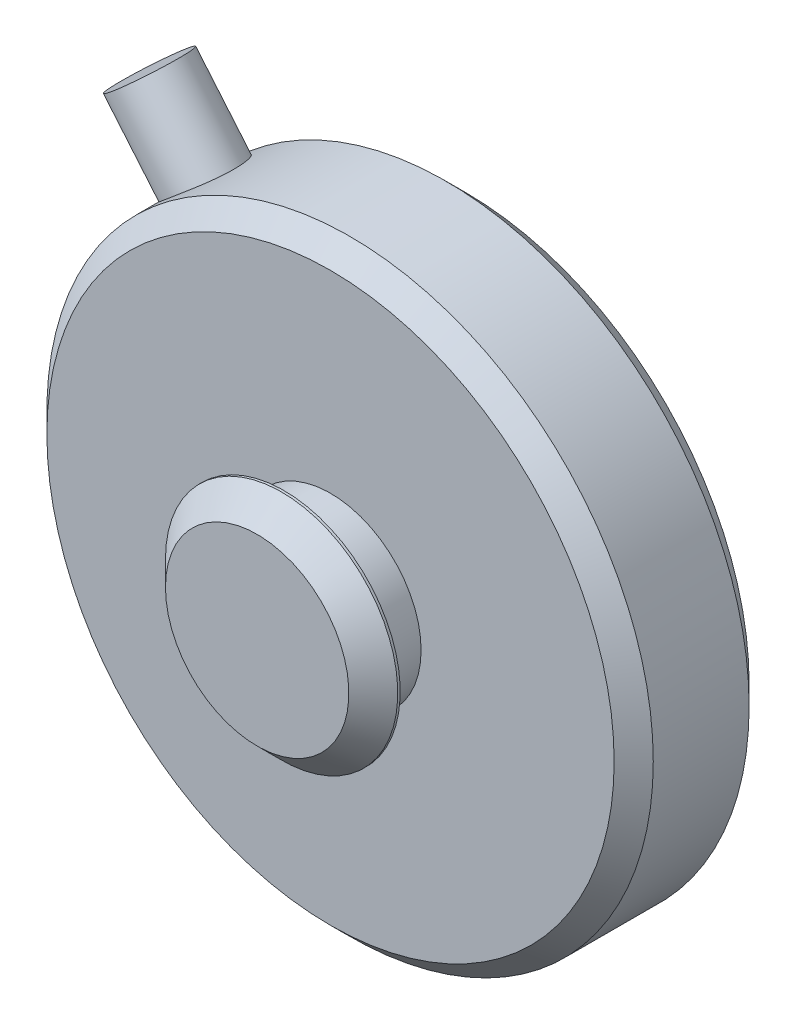
SolidWorks part; units mm, degrees
material "Plain Carbon Steel"
ref_plane "Front Plane" through (0, 0, 0) normal (0, 0, 1) x (1, 0, 0)
ref_plane "Top Plane" through (0, 0, 0) normal (0, 1, 0) x (1, 0, 0)
ref_plane "Right Plane" through (0, 0, 0) normal (1, 0, 0) x (0, 0, -1)
sketch "Sketch1" plane through (0, 0, 0) normal (0, 0, 1) x (1, 0, 0)
  circle A0 centre (0, 0) radius 157.48
  dimension "D1" = 314.96
extrude "Extrude1" add sketch "Sketch1" along normal blind 70.104
sketch "Sketch2" plane through (0, 0, 70.104) normal (0, 0, 1) x (1, 0, 0)
  circle A0 centre (0, 0) radius 47.0535
  dimension "D1" = 94.107
extrude "Extrude2" add sketch "Sketch2" along normal blind 24.13
sketch "Sketch3" plane through (0, 0, 0) normal (0, 0, -1) x (-1, 0, 0)
  circle A0 centre (0, 0) radius 15.0114
  dimension "D1" = 30.0228
extrude "Extrude3" add sketch "Sketch3" along normal blind 13.462
sketch "Sketch4" plane through (0, 0, -13.462) normal (0, 0, -1) x (-1, 0, 0)
  circle A0 centre (0, 0) radius 24.511
  dimension "D1" = 49.022
extrude "Extrude4" add sketch "Sketch4" along normal blind 6.35
sketch "Sketch5" plane through (0, 0, -19.812) normal (0, 0, -1) x (-1, 0, 0)
  circle A0 centre (0, 0) radius 15.875
  dimension "D1" = 31.75
extrude "Extrude5" add sketch "Sketch5" along normal blind 6.858
sketch "Sketch6" plane through (0, 0, 0) normal (0, 0, -1) x (-1, 0, 0)
  circle A0 centre (0, -38.1) radius 3.175
  dimension "D2" = 6.35
  dimension "D1" = 38.1
extrude "Cut-Extrude1" cut sketch "Sketch6" against normal blind 11.43
pattern_circular "CirPattern1" count 5 over 360 about axis through (0, 0, 70.104) along (0, 0, -1) of "Cut-Extrude1"
sketch "Sketch7" plane through (0, 0, 94.234) normal (0, 0, 1) x (1, 0, 0)
  circle A0 centre (0, 0) radius 60.325
  dimension "D1" = 120.65
extrude "Extrude6" add sketch "Sketch7" along normal blind 13.97
chamfer "Chamfer1" distance 10.16 angle 45 2 edges at (157.48, 0, 0) (157.48, 0, 70.104)
chamfer "Chamfer2" distance 12.7 angle 45 1 edges at (60.325, 0, 108.204)
ref_plane "Plane1" through (0, 0, 0) normal (0.766, 0.6428, 0) x (0, 0, -1)
ref_plane "Plane2" through (101.2262, -120.6367, 35.052) normal (0.6428, -0.766, 0) x (-0.766, -0.6428, 0)
ref_plane "Plane3" through (-101.2262, 120.6367, 0) normal (0.6428, -0.766, 0) x (0.766, 0.6428, 0)
sketch "Sketch8" plane through (-101.2262, 120.6367, 0) normal (0.6428, -0.766, 0) x (0.766, 0.6428, 0)
  line L6 (157.48, 10.16) -> (-157.48, 10.16) construction
  circle A0 centre (0, 34.29) radius 19.05
  dimension "D1" = 38.1
  dimension "D2" = 24.13
extrude "Extrude7" add sketch "Sketch8" along normal up to surface and the other way blind 44.45 up to face at (157.48, 0, 10.16)
